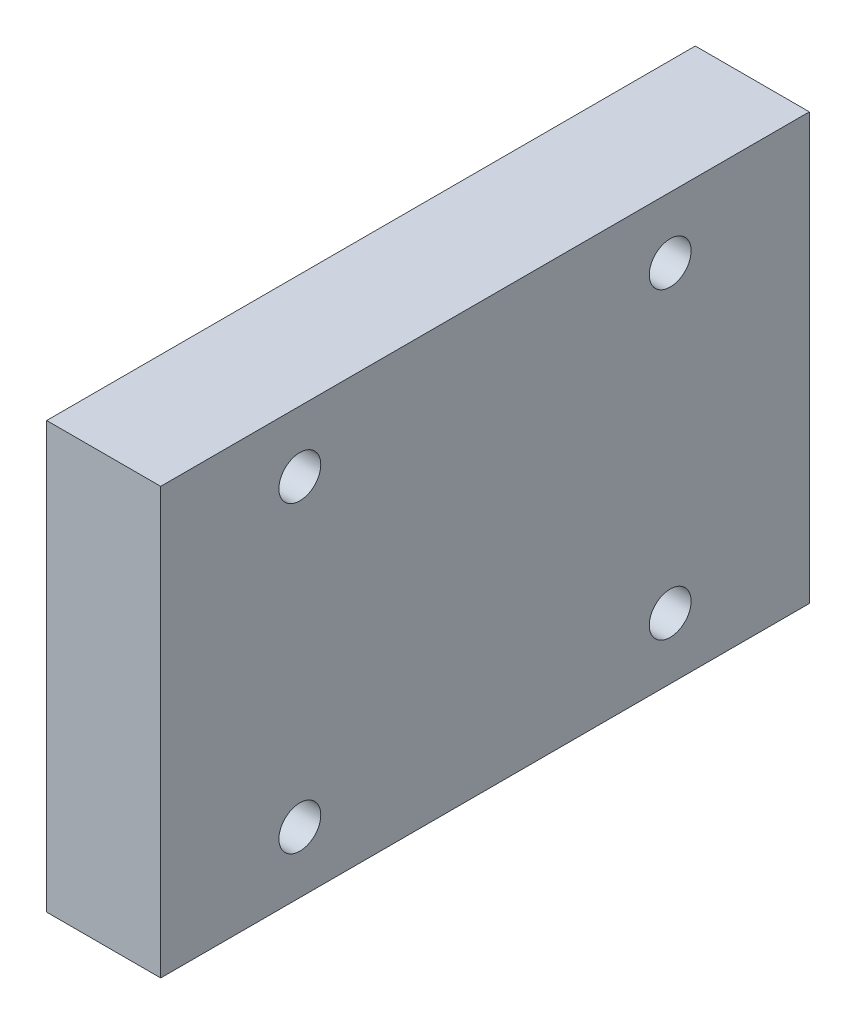
SolidWorks part; units mm, degrees
ref_plane "Front Plane" through (0, 0, 0) normal (0, 0, 1) x (1, 0, 0)
ref_plane "Top Plane" through (0, 0, 0) normal (0, 1, 0) x (1, 0, 0)
ref_plane "Right Plane" through (0, 0, 0) normal (1, 0, 0) x (0, 0, -1)
sketch "Sketch1" plane through (0, 0, 0) normal (1, 0, 0) x (0, 0, -1)
  line L0 (0, 10.175) -> (31, 10.175) construction
  line L1 (0, 0) -> (31, 0)
  line L2 (0, 0) -> (0, 20.35)
  line L3 (0, 20.35) -> (31, 20.35)
  line L4 (31, 0) -> (31, 20.35)
  line L6 (15.5, 20.35) -> (15.5, 0) construction
  circle A0 centre (6.65, 2.925) radius 1
  circle A1 centre (6.65, 17.425) radius 1
  circle A2 centre (24.35, 17.425) radius 1
  circle A3 centre (24.35, 2.925) radius 1
  point P13 (0, 0)
  point P16 (7.4997, 5.0265)
  point P19 (4.1306, 17.1393)
  point P20 (0, 0)
  point P21 (4.3713, 3.2618)
  point P22 (24.35, 17.425)
  dimension "D5" = 2
  dimension "D1" = 20.35
  dimension "D2" = 31
  dimension "D3" = 17.7
  dimension "D4" = 14.5
extrude "Boss-Extrude1" add sketch "Sketch1" along normal blind 5.45
